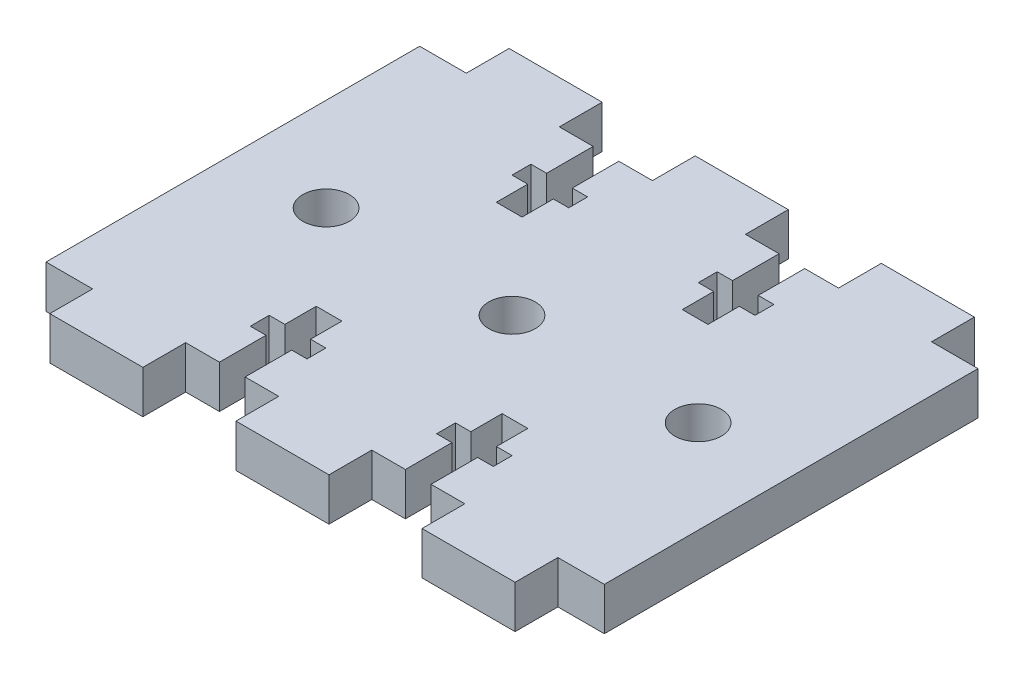
SolidWorks part; units mm, degrees
ref_plane "Front Plane" through (0, 0, 0) normal (0, 0, 1) x (1, 0, 0)
ref_plane "Top Plane" through (0, 0, 0) normal (0, 1, 0) x (1, 0, 0)
ref_plane "Right Plane" through (0, 0, 0) normal (1, 0, 0) x (0, 0, -1)
sketch "Sketch1" plane through (0, 0, 0) normal (0, 1, 0) x (1, 0, 0)
  line L0 (38.1, 0) -> (-38.1, 0) construction
  line L1 (38.1, -25.5) -> (31.7627, -25.5)
  line L2 (38.1, -25.5) -> (38.1, 25.5)
  line L3 (38.1, 25.5) -> (31.7627, 25.5)
  line L4 (-38.1, -25.5) -> (-38.1, 25.5)
  line L5 (38.1, -25.5) -> (-38.1, 25.5) construction
  line L6 (38.1, 25.5) -> (-38.1, -25.5) construction
  line L7 (0.0127, 25.3) -> (0.0127, -25.7) construction
  line L8 (-6.3373, 25.5) -> (-10.9221, 25.5)
  line L9 (6.3627, 31.342) -> (-6.3373, 31.342)
  line L10 (6.3627, 31.342) -> (6.3627, 25.5)
  line L11 (-31.7373, 25.5) -> (-38.1, 25.5)
  line L12 (-6.3373, 31.342) -> (-6.3373, 25.5)
  line L13 (6.3627, 31.342) -> (-6.3373, 25.5) construction
  line L14 (6.3627, 25.5) -> (-6.3373, 31.342) construction
  line L15 (31.7627, 31.342) -> (19.0627, 25.5) construction
  line L16 (-31.7373, 25.5) -> (-31.7373, 31.342)
  line L17 (-31.7373, 31.342) -> (-19.0373, 31.342)
  line L18 (-19.0373, 25.5) -> (-19.0373, 31.342)
  line L19 (-31.7373, 25.5) -> (-19.0373, 31.342) construction
  line L20 (-31.7373, 31.342) -> (-19.0373, 25.5) construction
  line L21 (31.7627, 25.5) -> (19.0627, 31.342) construction
  line L22 (19.0627, 25.5) -> (19.0627, 31.342)
  line L23 (31.7627, 31.342) -> (19.0627, 31.342)
  line L24 (31.7627, 25.5) -> (31.7627, 31.342)
  line L25 (19.0627, 25.5) -> (14.4526, 25.5)
  line L26 (-12.6747, 25.1) -> (-12.6747, 0) construction
  line L27 (12.7, 25.5) -> (12.7, -25.5) construction
  line L28 (-8.8313, 16.5719) -> (-8.8312, 19.15)
  line L29 (-14.4273, 16.5719) -> (-16.5688, 16.5719)
  line L30 (-10.9221, 19.15) -> (-10.9221, 25.5)
  line L31 (10.9474, 16.5719) -> (14.4526, 12.292) construction
  line L32 (-14.4273, 19.15) -> (-14.4273, 25.5)
  line L33 (-10.9221, 19.15) -> (-14.4273, 25.5) construction
  line L34 (-10.9221, 25.5) -> (-14.4273, 19.15) construction
  line L35 (-8.8313, 16.5719) -> (-10.9221, 16.5719)
  line L36 (-16.5688, 16.5719) -> (-16.5687, 19.15)
  line L37 (-8.8312, 19.15) -> (-10.9221, 19.15)
  line L38 (-14.4273, 19.15) -> (-16.5687, 19.15)
  line L39 (-14.4273, 25.5) -> (-19.0373, 25.5)
  line L40 (10.9474, 12.292) -> (14.4526, 16.5719) construction
  line L41 (-10.9221, 12.292) -> (-14.4273, 12.292)
  line L42 (-10.9221, 12.292) -> (-10.9221, 16.5719)
  line L43 (10.9474, 25.5) -> (14.4526, 19.15) construction
  line L44 (-14.4273, 12.292) -> (-14.4273, 16.5719)
  line L45 (-10.9221, 12.292) -> (-14.4273, 16.5719) construction
  line L46 (-10.9221, 16.5719) -> (-14.4273, 12.292) construction
  line L47 (10.9474, 19.15) -> (14.4526, 25.5) construction
  line L48 (14.4526, 12.292) -> (14.4526, 16.5719)
  line L49 (10.9474, 12.292) -> (10.9474, 16.5719)
  line L50 (10.9474, 12.292) -> (14.4526, 12.292)
  line L51 (14.4526, 19.15) -> (16.5941, 19.15)
  line L52 (8.8566, 19.15) -> (10.9474, 19.15)
  line L53 (16.5941, 16.5719) -> (16.5941, 19.15)
  line L54 (8.8566, 16.5719) -> (10.9474, 16.5719)
  line L55 (14.4526, 19.15) -> (14.4526, 25.5)
  line L56 (10.9474, 19.15) -> (10.9474, 25.5)
  line L57 (14.4526, 16.5719) -> (16.5941, 16.5719)
  line L58 (8.8566, 16.5719) -> (8.8566, 19.15)
  line L59 (10.9474, 25.5) -> (6.3627, 25.5)
  line L60 (10.9474, -19.15) -> (14.4526, -25.5) construction
  line L61 (10.9474, -25.5) -> (14.4526, -19.15) construction
  line L62 (10.9474, -12.292) -> (14.4526, -16.5719) construction
  line L63 (10.9474, -16.5719) -> (14.4526, -12.292) construction
  line L64 (8.8566, -16.5719) -> (8.8566, -19.15)
  line L65 (14.4526, -16.5719) -> (16.5941, -16.5719)
  line L66 (10.9474, -19.15) -> (10.9474, -25.5)
  line L67 (14.4526, -19.15) -> (14.4526, -25.5)
  line L68 (8.8566, -16.5719) -> (10.9474, -16.5719)
  line L69 (16.5941, -16.5719) -> (16.5941, -19.15)
  line L70 (8.8566, -19.15) -> (10.9474, -19.15)
  line L71 (14.4526, -19.15) -> (16.5941, -19.15)
  line L72 (10.9474, -12.292) -> (14.4526, -12.292)
  line L73 (10.9474, -12.292) -> (10.9474, -16.5719)
  line L74 (14.4526, -12.292) -> (14.4526, -16.5719)
  line L75 (-14.4273, -16.5719) -> (-16.5687, -16.5719)
  line L76 (-14.4273, -19.15) -> (-16.5687, -19.15)
  line L77 (-16.5687, -16.5719) -> (-16.5687, -19.15)
  line L78 (-10.9221, -16.5719) -> (-14.4273, -12.292) construction
  line L79 (-10.9221, -12.292) -> (-14.4273, -16.5719) construction
  line L80 (-10.9221, -25.5) -> (-14.4273, -19.15) construction
  line L81 (-10.9221, -19.15) -> (-14.4273, -25.5) construction
  line L82 (-14.4273, -12.292) -> (-14.4273, -16.5719)
  line L83 (-10.9221, -12.292) -> (-10.9221, -16.5719)
  line L84 (-10.9221, -12.292) -> (-14.4273, -12.292)
  line L85 (-8.8312, -19.15) -> (-10.9221, -19.15)
  line L86 (-8.8313, -16.5719) -> (-10.9221, -16.5719)
  line L87 (-14.4273, -19.15) -> (-14.4273, -25.5)
  line L88 (-10.9221, -19.15) -> (-10.9221, -25.5)
  line L89 (-8.8313, -16.5719) -> (-8.8312, -19.15)
  line L90 (-14.4273, -25.5) -> (-19.0373, -25.5)
  line L91 (10.9474, -25.5) -> (6.3627, -25.5)
  line L92 (-31.7373, -25.5) -> (-31.7373, -31.342)
  line L93 (-19.0373, -25.5) -> (-19.0373, -31.342)
  line L94 (-6.3373, -31.342) -> (-6.3373, -25.5)
  line L95 (6.3627, -31.342) -> (6.3627, -25.5)
  line L96 (19.0627, -25.5) -> (19.0627, -31.342)
  line L97 (31.7627, -25.5) -> (31.7627, -31.342)
  line L98 (31.7627, -31.342) -> (19.0627, -31.342)
  line L99 (-31.7373, -31.342) -> (-19.0373, -31.342)
  line L100 (6.3627, -31.342) -> (-6.3373, -31.342)
  line L101 (-31.7373, -25.5) -> (-38.1, -25.5)
  line L102 (-6.3373, -25.5) -> (-10.9221, -25.5)
  line L103 (19.0627, -25.5) -> (14.4526, -25.5)
  point P0 (0, 0)
  point P10 (0.0127, 28.421)
  point P15 (-25.3873, 28.421)
  point P24 (25.4127, 28.421)
  point P29 (-12.6747, 22.325)
  point P34 (-12.6747, 12.55)
  point P39 (-12.6747, 14.4319)
  point P56 (12.7, 14.4319)
  point P57 (12.7, 12.55)
  point P58 (12.7, 22.325)
  point P68 (12.7, 0)
  point P72 (12.7, -22.325)
  point P73 (12.7, -12.55)
  point P74 (12.7, -14.4319)
  point P87 (-12.6747, -14.4319)
  point P88 (-12.6747, -12.55)
  point P89 (-12.6747, -22.325)
  point P102 (25.4127, -28.421)
  point P103 (-25.3873, -28.421)
  point P104 (0.0127, -28.421)
  dimension "D1" = 76.2
  dimension "D2" = 51
  dimension "D3" = 12.7
  dimension "D4" = 5.842
  dimension "D5" = 12.7
  dimension "D6" = 5.842
  dimension "D7" = 25.4
  dimension "D8" = 3.5052
  dimension "D9" = 6.35
  dimension "D10" = 7.7375
  dimension "D11" = 2.5781
  dimension "D12" = 4.2799
extrude "Boss-Extrude1" add sketch "Sketch1" along normal blind 5.842
sketch "Sketch2" plane through (0, 5.842, 0) normal (0, 1, 0) x (1, 0, 0)
  line L0 (-38.1, 0) -> (38.1, 0) construction
  line L1 (-38.1, 25.5) -> (-38.1, -25.5) construction
  line L2 (38.1, -25.5) -> (38.1, 25.5) construction
  line L3 (0.0127, 31.342) -> (0.0127, -31.342) construction
  line L4 (6.3627, 31.342) -> (-6.3373, 31.342) construction
  line L5 (-6.3373, -31.342) -> (6.3627, -31.342) construction
  circle A0 centre (0, 0) radius 3.175
  circle A1 centre (25.4, 0) radius 3.175
  circle A2 centre (-25.3747, 0) radius 3.175
  dimension "D1" = 6.35
  dimension "D2" = 6.35
  dimension "D3" = 25.4
extrude "Cut-Extrude1" cut sketch "Sketch2" against normal through all
sketch "Sketch3" [suppressed] plane through (0, 5.842, 0) normal (0, 1, 0) x (1, 0, 0)
  line L0 (-38.1, 0) -> (38.1, 0) construction
  line L1 (-38.1, 25.5) -> (-38.1, -25.5) construction
  line L2 (38.1, -25.5) -> (38.1, 25.5) construction
  line L4 (-17.4625, -6.35) -> (-42.8625, -6.35)
  line L5 (-17.4625, -6.35) -> (-17.4625, 6.35)
  line L6 (-17.4625, 6.35) -> (-42.8625, 6.35)
  line L7 (-42.8625, -6.35) -> (-42.8625, 6.35)
  line L8 (-17.4625, -6.35) -> (-42.8625, 6.35) construction
  line L9 (-17.4625, 6.35) -> (-42.8625, -6.35) construction
  point P6 (-30.1625, 0)
  dimension "D1" = 12.7
  dimension "D2" = 25.4
  dimension "D3" = 7.9375
extrude "Cut-Extrude2" [suppressed] cut sketch "Sketch3" against normal through all
fillet "Fillet1" [suppressed] radius 0.7937
